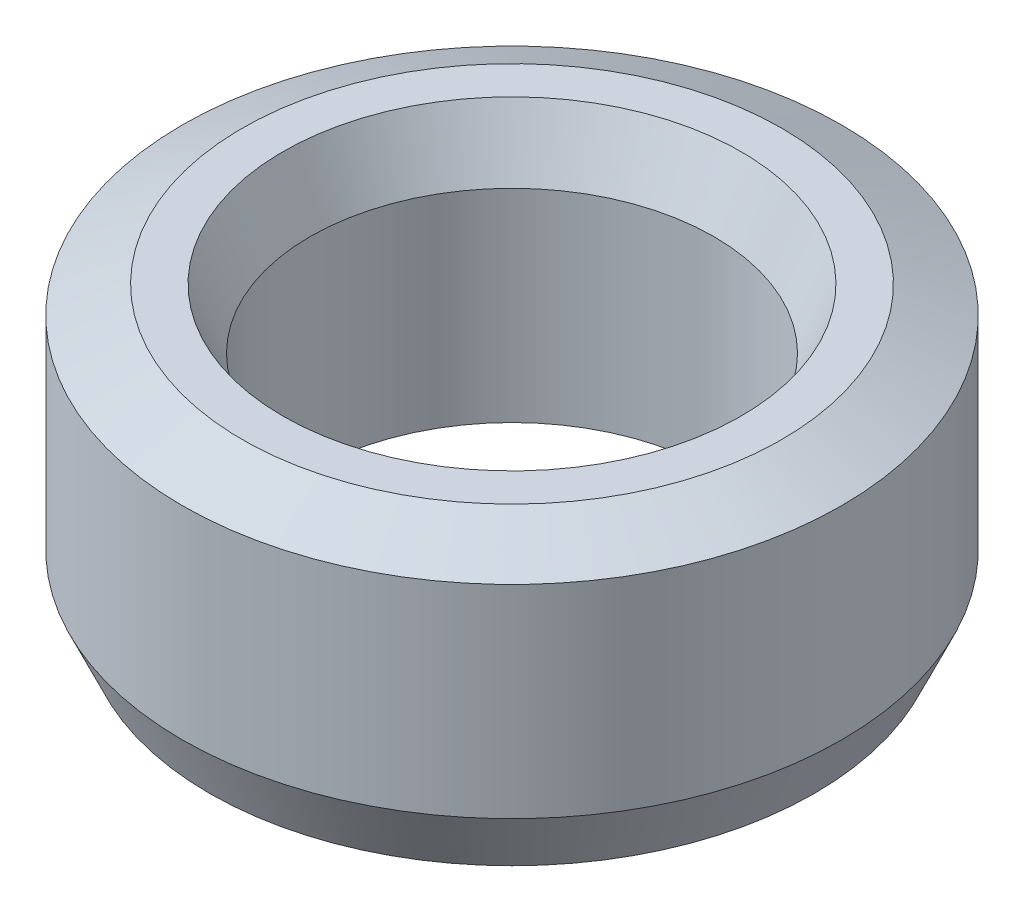
SolidWorks part; units mm, degrees
ref_plane "Front Plane" through (0, 0, 0) normal (0, 0, 1) x (1, 0, 0)
ref_plane "Top Plane" through (0, 0, 0) normal (0, 1, 0) x (1, 0, 0)
ref_plane "Right Plane" through (0, 0, 0) normal (1, 0, 0) x (0, 0, -1)
sketch "Sketch1" plane through (0, 0, 0) normal (0, 1, 0) x (1, 0, 0)
  circle A0 centre (0, 0) radius 37.5
  dimension "SLEEVE_OD" = 75
extrude "Boss-Extrude1" add sketch "Sketch1" along normal blind 32.9867
sketch "Sketch2" plane through (0, 0, 0) normal (0, 1, 0) x (1, 0, 0)
  circle A0 centre (0, 0) radius 22.9633
  dimension "BORE_D" = 45.9266
extrude "Cut-Extrude1" cut sketch "Sketch2" along normal through all
chamfer "Chamfer1" distance 3.0924 angle 65.613 4 edges at (0, 32.9867, 22.9633) (0, 0, 22.9633) (0, 0, 37.5) (0, 32.9867, 37.5) first distance on face at (0, 32.9867, 22.9633) first distance on face at (0, 0, 22.9633) first distance on face at (0, 32.9867, 37.5)
